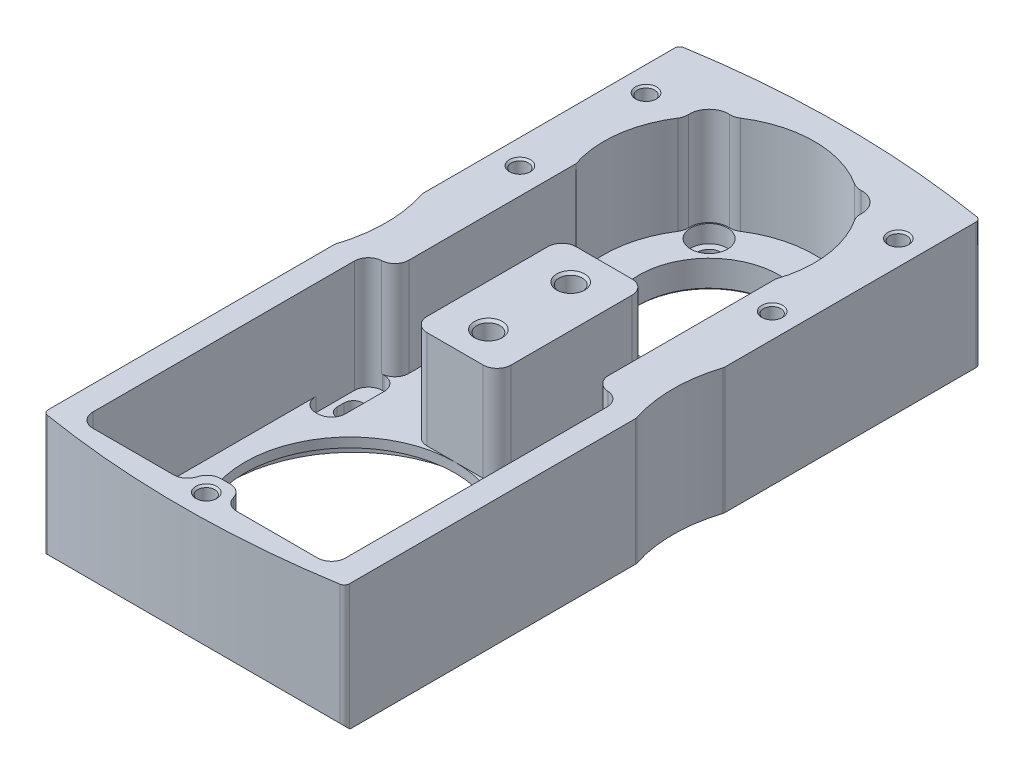
SolidWorks part; units mm, degrees
ref_plane "Front Plane" through (0, 0, 0) normal (0, 0, 1) x (1, 0, 0)
ref_plane "Top Plane" through (0, 0, 0) normal (0, 1, 0) x (1, 0, 0)
ref_plane "Right Plane" through (0, 0, 0) normal (1, 0, 0) x (0, 0, -1)
sketch "Sketch1" plane through (0, 0, 0) normal (0, 1, 0) x (1, 0, 0)
  line L0 (-43, 86.5221) -> (-43, 4.8795)
  line L1 (43, 4.8795) -> (43, 86.5221)
  line L2 (43, 111.9779) -> (43, 183.6205)
  line L3 (-43, 183.6205) -> (-43, 111.9779)
  arc A0 (-43, 4.8795) -> (-41.7427, 3.3992) centre (-41.5, 4.8795) ccw
  arc A1 (-41.7427, 3.3992) -> (41.7427, 3.3992) centre (0, 258) ccw
  arc A2 (41.7427, 3.3992) -> (43, 4.8795) centre (41.5, 4.8795) ccw
  arc A3 (43, 86.5221) -> (42.9277, 86.9821) centre (41.5, 86.5221) ccw
  arc A4 (42.9277, 86.9821) -> (42.9277, 111.5179) centre (81, 99.25) cw
  arc A5 (42.9277, 111.5179) -> (43, 111.9779) centre (41.5, 111.9779) ccw
  arc A6 (43, 183.6205) -> (41.7427, 185.1008) centre (41.5, 183.6205) ccw
  arc A7 (41.7427, 185.1008) -> (-41.7427, 185.1008) centre (0, -69.5) ccw
  arc A8 (-41.7427, 185.1008) -> (-43, 183.6205) centre (-41.5, 183.6205) ccw
  arc A9 (-43, 111.9779) -> (-42.9277, 111.5179) centre (-41.5, 111.9779) ccw
  arc A10 (-42.9277, 111.5179) -> (-42.9277, 86.9821) centre (-81, 99.25) cw
  arc A11 (-42.9277, 86.9821) -> (-43, 86.5221) centre (-41.5, 86.5221) ccw
extrude "Boss-Extrude1" add sketch "Sketch1" along normal blind 36
sketch "Sketch2" plane through (0, 0, 0) normal (1, 0, 0) x (0, 0, -1)
  line L0 (0, 5) -> (0, 0)
  line L1 (0, 0) -> (5, 0)
  line L2 (5, 0) -> (0, 5)
extrude "Cut-Extrude1" cut sketch "Sketch2" along normal blind 43 and the other way blind 43
ref_plane "Plane1" through (0, 36, 0) normal (0, 1, 0) x (1, 0, 0)
sketch "Sketch3" plane through (0, 36, 0) normal (0, 1, 0) x (1, 0, 0)
  line L0 (28.5, 57.5264) -> (28.5, 141.1325)
  line L1 (-28.5, 141.1325) -> (-28.5, 57.5264)
  line L2 (-12, 116.5) -> (-12, 82)
  line L3 (-8, 78) -> (8, 78)
  line L4 (12, 82) -> (12, 116.5)
  line L5 (8, 120.5) -> (-8, 120.5)
  arc A0 (-28.5, 57.5264) -> (28.5, 57.5264) centre (0, 48) ccw
  arc A1 (28.5, 141.1325) -> (-28.5, 141.1325) centre (0, 150.5) ccw
  arc A2 (-12, 82) -> (-8, 78) centre (-8, 82) ccw
  arc A3 (8, 78) -> (12, 82) centre (8, 82) ccw
  arc A4 (12, 116.5) -> (8, 120.5) centre (8, 116.5) ccw
  arc A5 (-8, 120.5) -> (-12, 116.5) centre (-8, 116.5) ccw
sketch "Sketch4" plane through (0, 0, 0) normal (1, 0, 0) x (0, 0, -1)
  line L0 (111, 36) -> (115, 36)
  line L1 (115, 36) -> (114.3235, 35.3235)
  line L2 (114.3235, 35.3235) -> (114.3235, 6)
  line L3 (114.3235, 6) -> (111, 4.0812)
  line L4 (111, 4.0812) -> (111, 36)
  line L5 (111, 4.0812) -> (111, 36) construction
revolve "Cut-Revolve1" cut sketch "Sketch4" angle 360 about L5 reverse direction yes
cosmetic thread "Cosmetic Thread1" parameters "D1"=25, "D2"=8
sketch "Sketch5" plane through (0, 0, 0) normal (1, 0, 0) x (0, 0, -1)
  line L0 (87.5, 36) -> (91.5, 36)
  line L1 (91.5, 36) -> (90.8235, 35.3235)
  line L2 (90.8235, 35.3235) -> (90.8235, 6)
  line L3 (90.8235, 6) -> (87.5, 4.0812)
  line L4 (87.5, 4.0812) -> (87.5, 36)
  line L5 (87.5, 4.0812) -> (87.5, 36) construction
revolve "Cut-Revolve2" cut sketch "Sketch5" angle 360 about L5 reverse direction yes
cosmetic thread "Cosmetic Thread2" parameters "D1"=25, "D2"=8
ref_plane "Plane2" through (-36, 0, 0) normal (1, 0, 0) x (0, 0, -1)
sketch "Sketch6" plane through (-36, 0, 0) normal (1, 0, 0) x (0, 0, -1)
  line L0 (168.5, 36) -> (171.5, 36)
  line L1 (171.5, 36) -> (170.9585, 35.4585)
  line L2 (170.9585, 35.4585) -> (170.9585, 14)
  line L3 (170.9585, 14) -> (168.5, 12.5806)
  line L4 (168.5, 12.5806) -> (168.5, 36)
  line L5 (168.5, 12.5806) -> (168.5, 36) construction
revolve "Cut-Revolve3" cut sketch "Sketch6" angle 360 about L5 reverse direction yes
cosmetic thread "Cosmetic Thread3" parameters "D1"=18, "D2"=6
sketch "Sketch7" plane through (-36, 0, 0) normal (1, 0, 0) x (0, 0, -1)
  line L0 (132.5, 36) -> (135.5, 36)
  line L1 (135.5, 36) -> (134.9585, 35.4585)
  line L2 (134.9585, 35.4585) -> (134.9585, 14)
  line L3 (134.9585, 14) -> (132.5, 12.5806)
  line L4 (132.5, 12.5806) -> (132.5, 36)
  line L5 (132.5, 12.5806) -> (132.5, 36) construction
revolve "Cut-Revolve4" cut sketch "Sketch7" angle 360 about L5 reverse direction yes
cosmetic thread "Cosmetic Thread4" parameters "D1"=18, "D2"=6
ref_plane "Plane3" through (36, 0, 0) normal (1, 0, 0) x (0, 0, -1)
sketch "Sketch8" plane through (36, 0, 0) normal (1, 0, 0) x (0, 0, -1)
  line L0 (168.5, 36) -> (171.5, 36)
  line L1 (171.5, 36) -> (170.9585, 35.4585)
  line L2 (170.9585, 35.4585) -> (170.9585, 14)
  line L3 (170.9585, 14) -> (168.5, 12.5806)
  line L4 (168.5, 12.5806) -> (168.5, 36)
  line L5 (168.5, 12.5806) -> (168.5, 36) construction
revolve "Cut-Revolve5" cut sketch "Sketch8" angle 360 about L5 reverse direction yes
cosmetic thread "Cosmetic Thread5" parameters "D1"=18, "D2"=6
sketch "Sketch9" plane through (36, 0, 0) normal (1, 0, 0) x (0, 0, -1)
  line L0 (132.5, 36) -> (135.5, 36)
  line L1 (135.5, 36) -> (134.9585, 35.4585)
  line L2 (134.9585, 35.4585) -> (134.9585, 14)
  line L3 (134.9585, 14) -> (132.5, 12.5806)
  line L4 (132.5, 12.5806) -> (132.5, 36)
  line L5 (132.5, 12.5806) -> (132.5, 36) construction
revolve "Cut-Revolve6" cut sketch "Sketch9" angle 360 about L5 reverse direction yes
cosmetic thread "Cosmetic Thread6" parameters "D1"=18, "D2"=6
sketch "Sketch10" plane through (0, 0, 0) normal (1, 0, 0) x (0, 0, -1)
  line L0 (7, 36) -> (10, 36)
  line L1 (10, 36) -> (9.4585, 35.4585)
  line L2 (9.4585, 35.4585) -> (9.4585, 14)
  line L3 (9.4585, 14) -> (7, 12.5806)
  line L4 (7, 12.5806) -> (7, 36)
  line L5 (7, 12.5806) -> (7, 36) construction
revolve "Cut-Revolve7" cut sketch "Sketch10" angle 360 about L5 reverse direction yes
cosmetic thread "Cosmetic Thread7" parameters "D1"=18, "D2"=6
sketch "Sketch11" plane through (0, 0, 0) normal (1, 0, 0) x (0, 0, -1)
  line L0 (150.5, 36) -> (170.5, 36)
  line L1 (170.5, 36) -> (170.5, 0.6)
  line L2 (170.5, 0.6) -> (171.1, 0)
  line L3 (171.1, 0) -> (150.5, 0)
  line L4 (150.5, 0) -> (150.5, 36)
  line L5 (150.5, 0) -> (150.5, 36) construction
revolve "Cut-Revolve8" cut sketch "Sketch11" angle 360 about L5 reverse direction yes
ref_plane "Plane4" through (19, 0, 0) normal (1, 0, 0) x (0, 0, -1)
sketch "Sketch12" plane through (19, 0, 0) normal (1, 0, 0) x (0, 0, -1)
  line L0 (131.5, 36) -> (136.75, 36)
  line L1 (136.75, 36) -> (136.75, 3)
  line L2 (136.75, 3) -> (134.8, 3)
  line L3 (134.8, 3) -> (134.8, 0)
  line L4 (134.8, 0) -> (131.5, 0)
  line L5 (131.5, 0) -> (131.5, 36)
  line L6 (131.5, 0) -> (131.5, 36) construction
revolve "Cut-Revolve9" cut sketch "Sketch12" angle 360 about L6 reverse direction yes
sketch "Sketch13" plane through (19, 0, 0) normal (1, 0, 0) x (0, 0, -1)
  line L0 (169.5, 36) -> (174.75, 36)
  line L1 (174.75, 36) -> (174.75, 3)
  line L2 (174.75, 3) -> (172.8, 3)
  line L3 (172.8, 3) -> (172.8, 0)
  line L4 (172.8, 0) -> (169.5, 0)
  line L5 (169.5, 0) -> (169.5, 36)
  line L6 (169.5, 0) -> (169.5, 36) construction
revolve "Cut-Revolve10" cut sketch "Sketch13" angle 360 about L6 reverse direction yes
ref_plane "Plane5" through (-19, 0, 0) normal (1, 0, 0) x (0, 0, -1)
sketch "Sketch14" plane through (-19, 0, 0) normal (1, 0, 0) x (0, 0, -1)
  line L0 (131.5, 36) -> (136.75, 36)
  line L1 (136.75, 36) -> (136.75, 3)
  line L2 (136.75, 3) -> (134.8, 3)
  line L3 (134.8, 3) -> (134.8, 0)
  line L4 (134.8, 0) -> (131.5, 0)
  line L5 (131.5, 0) -> (131.5, 36)
  line L6 (131.5, 0) -> (131.5, 36) construction
revolve "Cut-Revolve11" cut sketch "Sketch14" angle 360 about L6 reverse direction yes
sketch "Sketch15" plane through (-19, 0, 0) normal (1, 0, 0) x (0, 0, -1)
  line L0 (169.5, 36) -> (174.75, 36)
  line L1 (174.75, 36) -> (174.75, 3)
  line L2 (174.75, 3) -> (172.8, 3)
  line L3 (172.8, 3) -> (172.8, 0)
  line L4 (172.8, 0) -> (169.5, 0)
  line L5 (169.5, 0) -> (169.5, 36)
  line L6 (169.5, 0) -> (169.5, 36) construction
revolve "Cut-Revolve12" cut sketch "Sketch15" angle 360 about L6 reverse direction yes
sketch "Sketch16" plane through (0, 36, 0) normal (0, 1, 0) x (1, 0, 0)
  line L0 (31.5698, 6.6802) -> (32.0698, 6.6802)
  line L1 (36.0698, 10.6802) -> (36.0698, 21.6802)
  line L2 (32.0698, 25.6802) -> (31.5698, 25.6802)
  line L3 (27.5698, 21.6802) -> (27.5698, 10.6802)
  arc A0 (27.5698, 10.6802) -> (31.5698, 6.6802) centre (31.5698, 10.6802) ccw
  arc A1 (32.0698, 6.6802) -> (36.0698, 10.6802) centre (32.0698, 10.6802) ccw
  arc A2 (36.0698, 21.6802) -> (32.0698, 25.6802) centre (32.0698, 21.6802) ccw
  arc A3 (31.5698, 25.6802) -> (27.5698, 21.6802) centre (31.5698, 21.6802) ccw
extrude "Cut-Extrude2" cut sketch "Sketch16" against normal blind 32
sketch "Sketch17" plane through (0, 36, 0) normal (0, 1, 0) x (1, 0, 0)
  line L0 (31.5698, 70.3198) -> (32.0698, 70.3198)
  line L1 (36.0698, 74.3198) -> (36.0698, 85.3198)
  line L2 (32.0698, 89.3198) -> (31.5698, 89.3198)
  line L3 (27.5698, 85.3198) -> (27.5698, 74.3198)
  arc A0 (27.5698, 74.3198) -> (31.5698, 70.3198) centre (31.5698, 74.3198) ccw
  arc A1 (32.0698, 70.3198) -> (36.0698, 74.3198) centre (32.0698, 74.3198) ccw
  arc A2 (36.0698, 85.3198) -> (32.0698, 89.3198) centre (32.0698, 85.3198) ccw
  arc A3 (31.5698, 89.3198) -> (27.5698, 85.3198) centre (31.5698, 85.3198) ccw
extrude "Cut-Extrude3" cut sketch "Sketch17" against normal blind 32
sketch "Sketch18" plane through (0, 36, 0) normal (0, 1, 0) x (1, 0, 0)
  line L0 (-32.0698, 70.3198) -> (-31.5698, 70.3198)
  line L1 (-27.5698, 74.3198) -> (-27.5698, 85.3198)
  line L2 (-31.5698, 89.3198) -> (-32.0698, 89.3198)
  line L3 (-36.0698, 85.3198) -> (-36.0698, 74.3198)
  arc A0 (-36.0698, 74.3198) -> (-32.0698, 70.3198) centre (-32.0698, 74.3198) ccw
  arc A1 (-31.5698, 70.3198) -> (-27.5698, 74.3198) centre (-31.5698, 74.3198) ccw
  arc A2 (-27.5698, 85.3198) -> (-31.5698, 89.3198) centre (-31.5698, 85.3198) ccw
  arc A3 (-32.0698, 89.3198) -> (-36.0698, 85.3198) centre (-32.0698, 85.3198) ccw
extrude "Cut-Extrude4" cut sketch "Sketch18" against normal blind 32
sketch "Sketch19" plane through (0, 36, 0) normal (0, 1, 0) x (1, 0, 0)
  line L0 (-32.0698, 6.6802) -> (-31.5698, 6.6802)
  line L1 (-27.5698, 10.6802) -> (-27.5698, 21.6802)
  line L2 (-31.5698, 25.6802) -> (-32.0698, 25.6802)
  line L3 (-36.0698, 21.6802) -> (-36.0698, 10.6802)
  arc A0 (-36.0698, 10.6802) -> (-32.0698, 6.6802) centre (-32.0698, 10.6802) ccw
  arc A1 (-31.5698, 6.6802) -> (-27.5698, 10.6802) centre (-31.5698, 10.6802) ccw
  arc A2 (-27.5698, 21.6802) -> (-31.5698, 25.6802) centre (-31.5698, 21.6802) ccw
  arc A3 (-32.0698, 25.6802) -> (-36.0698, 21.6802) centre (-32.0698, 21.6802) ccw
extrude "Cut-Extrude5" cut sketch "Sketch19" against normal blind 32
sketch "Sketch20" plane through (0, 36, 0) normal (0, 1, 0) x (1, 0, 0)
  line L0 (34.4698, 15.1802) -> (34.4698, 17.1802)
  line L1 (29.1698, 17.1802) -> (29.1698, 15.1802)
  arc A0 (29.1698, 15.1802) -> (34.4698, 15.1802) centre (31.8198, 15.1802) ccw
  arc A1 (34.4698, 17.1802) -> (29.1698, 17.1802) centre (31.8198, 17.1802) ccw
extrude "Cut-Extrude6" cut sketch "Sketch20" against normal blind 36
sketch "Sketch21" plane through (0, 36, 0) normal (0, 1, 0) x (1, 0, 0)
  line L0 (34.4698, 78.8198) -> (34.4698, 80.8198)
  line L1 (29.1698, 80.8198) -> (29.1698, 78.8198)
  arc A0 (29.1698, 78.8198) -> (34.4698, 78.8198) centre (31.8198, 78.8198) ccw
  arc A1 (34.4698, 80.8198) -> (29.1698, 80.8198) centre (31.8198, 80.8198) ccw
extrude "Cut-Extrude7" cut sketch "Sketch21" against normal blind 36
sketch "Sketch22" plane through (0, 36, 0) normal (0, 1, 0) x (1, 0, 0)
  line L0 (-29.1698, 78.8198) -> (-29.1698, 80.8198)
  line L1 (-34.4698, 80.8198) -> (-34.4698, 78.8198)
  arc A0 (-34.4698, 78.8198) -> (-29.1698, 78.8198) centre (-31.8198, 78.8198) ccw
  arc A1 (-29.1698, 80.8198) -> (-34.4698, 80.8198) centre (-31.8198, 80.8198) ccw
extrude "Cut-Extrude8" cut sketch "Sketch22" against normal blind 36
sketch "Sketch23" plane through (0, 36, 0) normal (0, 1, 0) x (1, 0, 0)
  line L0 (-29.1698, 15.1802) -> (-29.1698, 17.1802)
  line L1 (-34.4698, 17.1802) -> (-34.4698, 15.1802)
  arc A0 (-34.4698, 15.1802) -> (-29.1698, 15.1802) centre (-31.8198, 15.1802) ccw
  arc A1 (-29.1698, 17.1802) -> (-34.4698, 17.1802) centre (-31.8198, 17.1802) ccw
extrude "Cut-Extrude9" cut sketch "Sketch23" against normal blind 36
sketch "Sketch24" plane through (0, 0, 0) normal (0, 1, 0) x (1, 0, 0)
  line L0 (35.25, 47) -> (35.25, 49)
  line L1 (-35.25, 49) -> (-35.25, 47)
  arc A0 (-35.25, 47) -> (35.25, 47) centre (0, 47) ccw
  arc A1 (35.25, 49) -> (-35.25, 49) centre (0, 49) ccw
extrude "Cut-Extrude10" cut sketch "Sketch24" along normal blind 5.3
extrude "Cut-Extrude11" cut sketch "Sketch3" against normal blind 28
sketch "Sketch25" plane through (0, 0, 0) normal (1, 0, 0) x (0, 0, -1)
  line L0 (48, 20) -> (78, 20)
  line L1 (78, 20) -> (78, 0)
  line L2 (78, 0) -> (48, 0)
  line L3 (48, 0) -> (48, 20)
  line L4 (48, 0) -> (48, 20) construction
revolve "Cut-Revolve13" cut sketch "Sketch25" angle 360 about L4 reverse direction yes
sketch "Sketch26" plane through (0, 36, 0) normal (0, 1, 0) x (1, 0, 0)
  line L0 (-36.0698, 85.3198) -> (-36.0698, 10.6802)
  line L1 (-32.0698, 6.6802) -> (-9, 6.6802)
  line L2 (-1.3028, 12.5) -> (1.3028, 12.5)
  line L3 (9, 6.6802) -> (32.0698, 6.6802)
  line L4 (36.0698, 10.6802) -> (36.0698, 85.3198)
  line L5 (28.5, 93.3082) -> (28.5, 140.9736)
  line L6 (-28.5, 140.9736) -> (-28.5, 93.3082)
  line L7 (-12, 116.5) -> (-12, 82)
  line L8 (-8, 78) -> (8, 78)
  line L9 (12, 82) -> (12, 116.5)
  line L10 (8, 120.5) -> (-8, 120.5)
  arc A0 (-36.0698, 10.6802) -> (-32.0698, 6.6802) centre (-32.0698, 10.6802) ccw
  arc A1 (-9, 6.6802) -> (-5.1514, 9.5901) centre (-9, 10.6802) ccw
  arc A2 (-5.1514, 9.5901) -> (-1.3028, 12.5) centre (-1.3028, 8.5) cw
  arc A3 (1.3028, 12.5) -> (5.1514, 9.5901) centre (1.3028, 8.5) cw
  arc A4 (5.1514, 9.5901) -> (9, 6.6802) centre (9, 10.6802) ccw
  arc A5 (32.0698, 6.6802) -> (36.0698, 10.6802) centre (32.0698, 10.6802) ccw
  arc A6 (36.0698, 85.3198) -> (32.2849, 89.314) centre (32.0698, 85.3198) ccw
  arc A7 (32.2849, 89.314) -> (28.5, 93.3082) centre (32.5, 93.3082) cw
  arc A8 (28.5, 140.9736) -> (25.2287, 166.8253) centre (0, 150.5) ccw
  arc A9 (25.2287, 166.8253) -> (24.5924, 169.2074) centre (28.5869, 168.9984) cw
  arc A10 (24.5924, 169.2074) -> (18.7074, 175.0924) centre (19, 169.5) ccw
  arc A11 (18.7074, 175.0924) -> (16.3253, 175.7287) centre (18.4984, 179.0869) cw
  arc A12 (16.3253, 175.7287) -> (-16.3253, 175.7287) centre (0, 150.5) ccw
  arc A13 (-16.3253, 175.7287) -> (-18.7074, 175.0924) centre (-18.4984, 179.0869) cw
  arc A14 (-18.7074, 175.0924) -> (-24.5924, 169.2074) centre (-19, 169.5) ccw
  arc A15 (-24.5924, 169.2074) -> (-25.2287, 166.8253) centre (-28.5869, 168.9984) cw
  arc A16 (-25.2287, 166.8253) -> (-28.5, 140.9736) centre (0, 150.5) ccw
  arc A17 (-28.5, 93.3082) -> (-32.2849, 89.314) centre (-32.5, 93.3082) cw
  arc A18 (-32.2849, 89.314) -> (-36.0698, 85.3198) centre (-32.0698, 85.3198) ccw
  arc A19 (-12, 82) -> (-8, 78) centre (-8, 82) ccw
  arc A20 (8, 78) -> (12, 82) centre (8, 82) ccw
  arc A21 (12, 116.5) -> (8, 120.5) centre (8, 116.5) ccw
  arc A22 (-8, 120.5) -> (-12, 116.5) centre (-8, 116.5) ccw
extrude "Cut-Extrude12" cut sketch "Sketch26" against normal blind 28
ref_plane "Plane6" through (0, 4, 0) normal (0, 1, 0) x (1, 0, 0)
ref_plane "Plane7" through (0, 3, 0) normal (0, 1, 0) x (1, 0, 0)
ref_plane "Plane8" through (0, 0, 0) normal (0, 1, 0) x (1, 0, 0)
ref_plane "Plane9" through (0, -8, 0) normal (0, 1, 0) x (1, 0, 0)
ref_plane "Plane10" through (0, 9, 0) normal (0, 1, 0) x (1, 0, 0)
ref_plane "Plane11" through (0, 9, 0) normal (0, 1, 0) x (1, 0, 0)
ref_plane "ANBAU XY" through (0, 0, 0) normal (0, 1, 0) x (1, 0, 0)
ref_plane "ANBAU XZ" through (0, 0, -150.5) normal (0, 0, 1) x (1, 0, 0)
ref_plane "ANBAU YZ" through (0, 0, 0) normal (1, 0, 0) x (0, 0, -1)
ref_axis "ANBAU X" through (-80.9, 0, -150.5) along (1, 0, 0)
ref_axis "ANBAU Y" through (0, 0, 50) along (0, 0, -1)
ref_axis "ANBAU Z" through (0, 50, -150.5) along (0, -1, 0)
sketch3d "ANBAU"
  point P0 (0, 0, -150.5)
ref_plane "AS 1 XY" through (0, 3, 0) normal (0, 1, 0) x (1, 0, 0)
ref_plane "AS 1 XZ" through (0, 0, -131.5) normal (0, 0, 1) x (1, 0, 0)
ref_plane "AS 1 YZ" through (19, 0, 0) normal (1, 0, 0) x (0, 0, -1)
ref_axis "AS 1 X" through (-80.9, 3, -131.5) along (1, 0, 0)
ref_axis "AS 1 Y" through (19, 3, 50) along (0, 0, -1)
ref_axis "AS 1 Z" through (19, 50, -131.5) along (0, -1, 0)
sketch3d "AS 1"
  point P0 (19, 3, -131.5)
ref_plane "AS 2 XY" through (0, 3, 0) normal (0, 1, 0) x (1, 0, 0)
ref_plane "AS 2 XZ" through (0, 0, -169.5) normal (0, 0, 1) x (1, 0, 0)
ref_plane "AS 2 YZ" through (19, 0, 0) normal (1, 0, 0) x (0, 0, -1)
ref_axis "AS 2 X" through (-80.9, 3, -169.5) along (1, 0, 0)
ref_axis "AS 2 Y" through (19, 3, 50) along (0, 0, -1)
ref_axis "AS 2 Z" through (19, 50, -169.5) along (0, -1, 0)
sketch3d "AS 2"
  point P0 (19, 3, -169.5)
ref_plane "AS 3 XY" through (0, 3, 0) normal (0, 1, 0) x (1, 0, 0)
ref_plane "AS 3 XZ" through (0, 0, -131.5) normal (0, 0, 1) x (1, 0, 0)
ref_plane "AS 3 YZ" through (-19, 0, 0) normal (1, 0, 0) x (0, 0, -1)
ref_axis "AS 3 X" through (-80.9, 3, -131.5) along (1, 0, 0)
ref_axis "AS 3 Y" through (-19, 3, 50) along (0, 0, -1)
ref_axis "AS 3 Z" through (-19, 50, -131.5) along (0, -1, 0)
sketch3d "AS 3"
  point P0 (-19, 3, -131.5)
ref_plane "AS 4 XY" through (0, 3, 0) normal (0, 1, 0) x (1, 0, 0)
ref_plane "AS 4 XZ" through (0, 0, -169.5) normal (0, 0, 1) x (1, 0, 0)
ref_plane "AS 4 YZ" through (-19, 0, 0) normal (1, 0, 0) x (0, 0, -1)
ref_axis "AS 4 X" through (-80.9, 3, -169.5) along (1, 0, 0)
ref_axis "AS 4 Y" through (-19, 3, 50) along (0, 0, -1)
ref_axis "AS 4 Z" through (-19, 50, -169.5) along (0, -1, 0)
sketch3d "AS 4"
  point P0 (-19, 3, -169.5)
ref_plane "DM XY" through (0, 0, 0) normal (0, 1, 0) x (1, 0, 0)
ref_plane "DM XZ" through (0, 0, -48) normal (0, 0, 1) x (1, 0, 0)
ref_plane "DM YZ" through (0, 0, 0) normal (1, 0, 0) x (0, 0, -1)
ref_axis "DM X" through (-80.9, 0, -48) along (1, 0, 0)
ref_axis "DM Y" through (0, 0, 50) along (0, 0, -1)
ref_axis "DM Z" through (0, 50, -48) along (0, -1, 0)
sketch3d "DM"
  point P0 (0, 0, -48)
ref_plane "MS 1 XY" through (0, -8, 0) normal (0, 1, 0) x (1, 0, 0)
ref_plane "MS 1 XZ" through (0, 0, -16.1802) normal (0, 0, 1) x (1, 0, 0)
ref_plane "MS 1 YZ" through (31.8198, 0, 0) normal (1, 0, 0) x (0, 0, -1)
ref_axis "MS 1 X" through (-80.9, -8, -16.1802) along (1, 0, 0)
ref_axis "MS 1 Y" through (31.8198, -8, 50) along (0, 0, -1)
ref_axis "MS 1 Z" through (31.8198, 50, -16.1802) along (0, -1, 0)
sketch3d "MS 1"
  point P0 (31.8198, -8, -16.1802)
ref_plane "MS 2 XY" through (0, -8, 0) normal (0, 1, 0) x (1, 0, 0)
ref_plane "MS 2 XZ" through (0, 0, -79.8198) normal (0, 0, 1) x (1, 0, 0)
ref_plane "MS 2 YZ" through (31.8198, 0, 0) normal (1, 0, 0) x (0, 0, -1)
ref_axis "MS 2 X" through (-80.9, -8, -79.8198) along (1, 0, 0)
ref_axis "MS 2 Y" through (31.8198, -8, 50) along (0, 0, -1)
ref_axis "MS 2 Z" through (31.8198, 50, -79.8198) along (0, -1, 0)
sketch3d "MS 2"
  point P0 (31.8198, -8, -79.8198)
ref_plane "MS 3 XY" through (0, -8, 0) normal (0, 1, 0) x (1, 0, 0)
ref_plane "MS 3 XZ" through (0, 0, -79.8198) normal (0, 0, 1) x (1, 0, 0)
ref_plane "MS 3 YZ" through (-31.8198, 0, 0) normal (1, 0, 0) x (0, 0, -1)
ref_axis "MS 3 X" through (-80.9, -8, -79.8198) along (1, 0, 0)
ref_axis "MS 3 Y" through (-31.8198, -8, 50) along (0, 0, -1)
ref_axis "MS 3 Z" through (-31.8198, 50, -79.8198) along (0, -1, 0)
sketch3d "MS 3"
  point P0 (-31.8198, -8, -79.8198)
ref_plane "MS 4 XY" through (0, -8, 0) normal (0, 1, 0) x (1, 0, 0)
ref_plane "MS 4 XZ" through (0, 0, -16.1802) normal (0, 0, 1) x (1, 0, 0)
ref_plane "MS 4 YZ" through (-31.8198, 0, 0) normal (1, 0, 0) x (0, 0, -1)
ref_axis "MS 4 X" through (-80.9, -8, -16.1802) along (1, 0, 0)
ref_axis "MS 4 Y" through (-31.8198, -8, 50) along (0, 0, -1)
ref_axis "MS 4 Z" through (-31.8198, 50, -16.1802) along (0, -1, 0)
sketch3d "MS 4"
  point P0 (-31.8198, -8, -16.1802)
ref_plane "NABE_AXIS XY" through (0, 9, 0) normal (0, 1, 0) x (1, 0, 0)
ref_plane "NABE_AXIS XZ" through (0, 0, -150.5) normal (0, 0, 1) x (1, 0, 0)
ref_plane "NABE_AXIS YZ" through (0, 0, 0) normal (1, 0, 0) x (0, 0, -1)
ref_axis "NABE_AXIS X" through (-80.9, 9, -150.5) along (1, 0, 0)
ref_axis "NABE_AXIS Y" through (0, 9, 50) along (0, 0, -1)
ref_axis "NABE_AXIS Z" through (0, 50, -150.5) along (0, -1, 0)
sketch3d "NABE_AXIS"
  point P0 (0, 9, -150.5)
ref_plane "NABE_MOT XY" through (0, 9, 0) normal (0, 1, 0) x (1, 0, 0)
ref_plane "NABE_MOT XZ" through (0, 0, -48) normal (0, 0, 1) x (1, 0, 0)
ref_plane "NABE_MOT YZ" through (0, 0, 0) normal (1, 0, 0) x (0, 0, -1)
ref_axis "NABE_MOT X" through (-80.9, 9, -48) along (1, 0, 0)
ref_axis "NABE_MOT Y" through (0, 9, 50) along (0, 0, -1)
ref_axis "NABE_MOT Z" through (0, 50, -48) along (0, -1, 0)
sketch3d "NABE_MOT"
  point P0 (0, 9, -48)
ref_plane "OBERTEIL XY" through (0, 36, 0) normal (0, 1, 0) x (1, 0, 0)
ref_plane "OBERTEIL XZ" through (0, 0, -150.5) normal (0, 0, 1) x (1, 0, 0)
ref_plane "OBERTEIL YZ" through (0, 0, 0) normal (1, 0, 0) x (0, 0, -1)
ref_axis "OBERTEIL X" through (-80.9, 36, -150.5) along (1, 0, 0)
ref_axis "OBERTEIL Y" through (0, 36, 50) along (0, 0, -1)
ref_axis "OBERTEIL Z" through (0, 50, -150.5) along (0, -1, 0)
sketch3d "OBERTEIL"
  point P0 (0, 36, -150.5)
ref_plane "SM 1 XY" through (0, 0, 0) normal (0, 1, 0) x (1, 0, 0)
ref_plane "SM 1 XZ" through (0, 0, -16.1802) normal (0, 0, 1) x (1, 0, 0)
ref_plane "SM 1 YZ" through (31.8198, 0, 0) normal (1, 0, 0) x (0, 0, -1)
ref_axis "SM 1 X" through (-80.9, 0, -16.1802) along (1, 0, 0)
ref_axis "SM 1 Y" through (31.8198, 0, 50) along (0, 0, -1)
ref_axis "SM 1 Z" through (31.8198, 50, -16.1802) along (0, -1, 0)
sketch3d "SM 1"
  point P0 (31.8198, 0, -16.1802)
ref_plane "SM 2 XY" through (0, 0, 0) normal (0, 1, 0) x (1, 0, 0)
ref_plane "SM 2 XZ" through (0, 0, -79.8198) normal (0, 0, 1) x (1, 0, 0)
ref_plane "SM 2 YZ" through (31.8198, 0, 0) normal (1, 0, 0) x (0, 0, -1)
ref_axis "SM 2 X" through (-80.9, 0, -79.8198) along (1, 0, 0)
ref_axis "SM 2 Y" through (31.8198, 0, 50) along (0, 0, -1)
ref_axis "SM 2 Z" through (31.8198, 50, -79.8198) along (0, -1, 0)
sketch3d "SM 2"
  point P0 (31.8198, 0, -79.8198)
ref_plane "SM 3 XY" through (0, 0, 0) normal (0, 1, 0) x (1, 0, 0)
ref_plane "SM 3 XZ" through (0, 0, -79.8198) normal (0, 0, 1) x (1, 0, 0)
ref_plane "SM 3 YZ" through (-31.8198, 0, 0) normal (1, 0, 0) x (0, 0, -1)
ref_axis "SM 3 X" through (-80.9, 0, -79.8198) along (1, 0, 0)
ref_axis "SM 3 Y" through (-31.8198, 0, 50) along (0, 0, -1)
ref_axis "SM 3 Z" through (-31.8198, 50, -79.8198) along (0, -1, 0)
sketch3d "SM 3"
  point P0 (-31.8198, 0, -79.8198)
ref_plane "SM 4 XY" through (0, 0, 0) normal (0, 1, 0) x (1, 0, 0)
ref_plane "SM 4 XZ" through (0, 0, -16.1802) normal (0, 0, 1) x (1, 0, 0)
ref_plane "SM 4 YZ" through (-31.8198, 0, 0) normal (1, 0, 0) x (0, 0, -1)
ref_axis "SM 4 X" through (-80.9, 0, -16.1802) along (1, 0, 0)
ref_axis "SM 4 Y" through (-31.8198, 0, 50) along (0, 0, -1)
ref_axis "SM 4 Z" through (-31.8198, 50, -16.1802) along (0, -1, 0)
sketch3d "SM 4"
  point P0 (-31.8198, 0, -16.1802)
ref_plane "VM 1 XY" through (0, 4, 0) normal (0, 1, 0) x (1, 0, 0)
ref_plane "VM 1 XZ" through (0, 0, -16.1802) normal (0, 0, 1) x (1, 0, 0)
ref_plane "VM 1 YZ" through (31.8198, 0, 0) normal (1, 0, 0) x (0, 0, -1)
ref_axis "VM 1 X" through (-80.9, 4, -16.1802) along (1, 0, 0)
ref_axis "VM 1 Y" through (31.8198, 4, 50) along (0, 0, -1)
ref_axis "VM 1 Z" through (31.8198, 50, -16.1802) along (0, -1, 0)
sketch3d "VM 1"
  point P0 (31.8198, 4, -16.1802)
ref_plane "VM 2 XY" through (0, 4, 0) normal (0, 1, 0) x (1, 0, 0)
ref_plane "VM 2 XZ" through (0, 0, -79.8198) normal (0, 0, 1) x (1, 0, 0)
ref_plane "VM 2 YZ" through (31.8198, 0, 0) normal (1, 0, 0) x (0, 0, -1)
ref_axis "VM 2 X" through (-80.9, 4, -79.8198) along (1, 0, 0)
ref_axis "VM 2 Y" through (31.8198, 4, 50) along (0, 0, -1)
ref_axis "VM 2 Z" through (31.8198, 50, -79.8198) along (0, -1, 0)
sketch3d "VM 2"
  point P0 (31.8198, 4, -79.8198)
ref_plane "VM 3 XY" through (0, 4, 0) normal (0, 1, 0) x (1, 0, 0)
ref_plane "VM 3 XZ" through (0, 0, -79.8198) normal (0, 0, 1) x (1, 0, 0)
ref_plane "VM 3 YZ" through (-31.8198, 0, 0) normal (1, 0, 0) x (0, 0, -1)
ref_axis "VM 3 X" through (-80.9, 4, -79.8198) along (1, 0, 0)
ref_axis "VM 3 Y" through (-31.8198, 4, 50) along (0, 0, -1)
ref_axis "VM 3 Z" through (-31.8198, 50, -79.8198) along (0, -1, 0)
sketch3d "VM 3"
  point P0 (-31.8198, 4, -79.8198)
ref_plane "VM 4 XY" through (0, 4, 0) normal (0, 1, 0) x (1, 0, 0)
ref_plane "VM 4 XZ" through (0, 0, -16.1802) normal (0, 0, 1) x (1, 0, 0)
ref_plane "VM 4 YZ" through (-31.8198, 0, 0) normal (1, 0, 0) x (0, 0, -1)
ref_axis "VM 4 X" through (-80.9, 4, -16.1802) along (1, 0, 0)
ref_axis "VM 4 Y" through (-31.8198, 4, 50) along (0, 0, -1)
ref_axis "VM 4 Z" through (-31.8198, 50, -16.1802) along (0, -1, 0)
sketch3d "VM 4"
  point P0 (-31.8198, 4, -16.1802)
ref_plane "ZR XY" through (0, 0, 0) normal (0, 1, 0) x (1, 0, 0)
ref_plane "ZR XZ" through (0, 0, -150.5) normal (0, 0, 1) x (1, 0, 0)
ref_plane "ZR YZ" through (0, 0, 0) normal (1, 0, 0) x (0, 0, -1)
ref_axis "ZR X" through (-80.9, 0, -150.5) along (1, 0, 0)
ref_axis "ZR Y" through (0, 0, 50) along (0, 0, -1)
ref_axis "ZR Z" through (0, 50, -150.5) along (0, -1, 0)
sketch3d "ZR"
  point P0 (0, 0, -150.5)
other "Freeze***"
